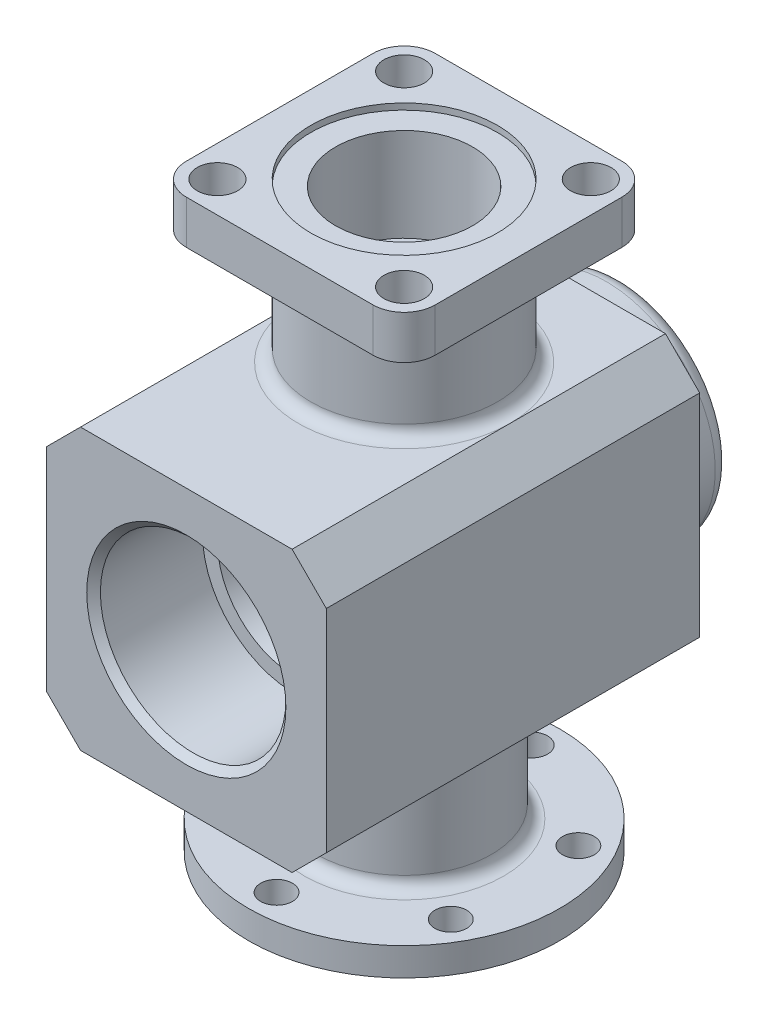
SolidWorks part; units mm, degrees
material "БрАЖ9-4 ГОСТ 18175-78"
ref_plane "Спереди" through (0, 0, 0) normal (0, 0, 1) x (1, 0, 0)
ref_plane "Сверху" through (0, 0, 0) normal (0, 1, 0) x (1, 0, 0)
ref_plane "Справа" through (0, 0, 0) normal (1, 0, 0) x (0, 0, -1)
sketch "Эскиз1" plane through (0, 0, 0) normal (0, 0, 1) x (1, 0, 0)
  line L1 (-45, -45) -> (45, -45)
  line L2 (-45, -45) -> (-45, 45)
  line L3 (-45, 45) -> (45, 45)
  line L4 (45, -45) -> (45, 45)
  line L5 (-45, -45) -> (45, 45) construction
  line L6 (-45, 45) -> (45, -45) construction
  point P0 (0, 0)
  dimension "D1" = 90
extrude "Бобышка-Вытянуть1" add sketch "Эскиз1" along normal blind 120
sketch "Эскиз9" plane through (0, 0, 0) normal (0, 0, -1) x (-1, 0, 0)
  circle A0 centre (0, 0) radius 35
  dimension "D1" = 70
extrude "Бобышка-Вытянуть6" add sketch "Эскиз9" along normal blind 20
sketch "Эскиз2" plane through (0, 45, 0) normal (0, 1, 0) x (1, 0, 0)
  line L0 (0, 20) -> (0, -120) construction
  line L1 (45, -120) -> (-45, -120) construction
  line L2 (35, 20) -> (-35, 20) construction
  circle A0 centre (0, -50) radius 30
  dimension "D1" = 60
extrude "Бобышка-Вытянуть2" add sketch "Эскиз2" along normal blind 51
sketch "Эскиз3" plane through (0, 96, 0) normal (0, 1, 0) x (1, 0, 0)
  line L1 (-40, -90) -> (40, -90)
  line L2 (-40, -90) -> (-40, -10)
  line L3 (-40, -10) -> (40, -10)
  line L4 (40, -90) -> (40, -10)
  line L5 (-40, -90) -> (40, -10) construction
  line L6 (-40, -10) -> (40, -90) construction
  point P0 (0, -50)
  dimension "D1" = 80
extrude "Бобышка-Вытянуть3" add sketch "Эскиз3" against normal blind 14
sketch "Эскиз4" plane through (0, -45, 0) normal (0, -1, 0) x (1, 0, 0)
  line L0 (0, 120) -> (0, -20) construction
  line L1 (-45, 120) -> (45, 120) construction
  line L2 (-35, -20) -> (35, -20) construction
  circle A0 centre (0, 50) radius 28
  dimension "D1" = 56
extrude "Бобышка-Вытянуть4" add sketch "Эскиз4" along normal blind 46
sketch "Эскиз5" plane through (0, -91, 0) normal (0, -1, 0) x (1, 0, 0)
  circle A0 centre (0, 50) radius 50
  dimension "D1" = 100
extrude "Бобышка-Вытянуть5" add sketch "Эскиз5" against normal blind 9
sketch "Эскиз6" plane through (0, -91, 0) normal (0, -1, 0) x (-1, 0, 0)
  circle A0 centre (0, -50) radius 15
  dimension "D1" = 30
extrude "Вырез-Вытянуть1" cut sketch "Эскиз6" against normal through all
sketch "Эскиз7" plane through (0, 96, 0) normal (0, 1, 0) x (1, 0, 0)
  circle A0 centre (0, -50) radius 22
  dimension "D1" = 44
extrude "Вырез-Вытянуть2" cut sketch "Эскиз7" against normal blind 32
fillet "Скругление1" radius 10 4 edges at (-40, 89, 10) (40, 89, 10) (40, 89, 90) (-40, 89, 90)
sketch "Эскиз10" plane through (0, 96, 0) normal (0, 1, 0) x (1, 0, 0)
  line L1 (-30, -80) -> (30, -80) construction
  line L2 (-30, -80) -> (-30, -20) construction
  line L3 (-30, -20) -> (30, -20) construction
  line L4 (30, -80) -> (30, -20) construction
  line L5 (-30, -80) -> (30, -20) construction
  line L6 (-30, -20) -> (30, -80) construction
  circle A0 centre (-30, -20) radius 6.5
  circle A1 centre (30, -80) radius 6.5
  circle A2 centre (30, -20) radius 6.5
  circle A3 centre (-30, -80) radius 6.5
  point P2 (0, -50)
  dimension "D2" = 13
  dimension "D1" = 60
extrude "Вырез-Вытянуть4" cut sketch "Эскиз10" against normal up to surface (14 mm away) up to face at (0, 82, 50)
chamfer "Фаска1" distance 11 angle 45 4 edges at (45, -45, 60) (-45, -45, 60) (-45, 45, 60) (45, 45, 60)
fillet "Скругление2" radius 5 2 edges at (-35, 0, 0) (-35, 0, -20)
sketch "Эскиз11" plane through (0, 0, 120) normal (0, 0, 1) x (1, 0, 0)
  circle A0 centre (0, 0) radius 29.805
  dimension "D1" = 59.61
extrude "Вырез-Вытянуть5" cut sketch "Эскиз11" against normal blind 35 contours A0
cosmetic thread "Условное изображение резьбы1" parameters "D1"=20, "D2"=64
sketch "Эскиз13" plane through (0, 0, 0) normal (1, 0, 0) x (0, 0, -1)
  line L0 (0, 0) -> (-120, 0) construction
  line L1 (0, 34) -> (0, -34) construction
  line L2 (-120, 29.805) -> (-120, -29.805) construction
  line L3 (-85, 25) -> (5, 12.3513)
  line L4 (-85, 29.805) -> (-85, -29.805) construction
  line L5 (5, 12.3513) -> (5, 0)
  line L6 (5, 0) -> (-85, 0)
  line L7 (-85, 0) -> (-85, 25)
  dimension "D1" = 50
  dimension "D2" = 90
  dimension "D3" = 8
revolve "Вырез-Повернуть1" cut sketch "Эскиз13" angle 360 about L0
chamfer "Фаска2" distance 2.195 angle 45 1 edges at (29.805, 0, 120)
sketch "Эскиз14" plane through (0, 96, 0) normal (0, 1, 0) x (1, 0, 0)
  circle A0 centre (0, -50) radius 30
  point P0 (0, -50)
  dimension "D1" = 60
extrude "Вырез-Вытянуть6" cut sketch "Эскиз14" against normal blind 2
fillet "Скругление3" radius 4 4 edges at (0, 82, 20) (0, -82, 22) (0, -45, 78) (0, 45, 20)
sketch "Эскиз15" plane through (0, -91, 0) normal (0, -1, 0) x (1, 0, 0)
  circle A0 centre (0, 50) radius 32 construction
  circle A1 centre (0, 50) radius 50 construction
  circle A2 centre (0, 50) radius 32 construction
  circle A3 centre (0, 50) radius 50 construction
  circle A4 centre (0, 50) radius 41 construction
  circle A5 centre (0, 91) radius 5.1
  dimension "D1" = 100
  dimension "D2" = 64
  dimension "D3" = 82
  dimension "D4" = 10.2
extrude "Вырез-Вытянуть7" cut sketch "Эскиз15" against normal up to surface (9 mm away) contours A5 up to face at (0, -82, 18)
sketch "Эскиз16" plane through (0, -91, 0) normal (0, -1, 0) x (1, 0, 0)
  circle A0 centre (0, 50) radius 28 construction
  circle A1 centre (0, 50) radius 28 construction
  circle A2 centre (0, 50) radius 24.5
  circle A3 centre (0, 50) radius 30.5
  dimension "D1" = 49
  dimension "D2" = 61
extrude "Вырез-Вытянуть8" cut sketch "Эскиз16" against normal blind 5.8
pattern_circular "Круговой массив2" count 6 over 360 about axis through (0, -82, 50) along (0, -1, 0) of "Вырез-Вытянуть7"
equation "\"D3@Эскиз15\"=0.5*(\"D1@Эскиз15\"+\"D2@Эскиз15\")"
